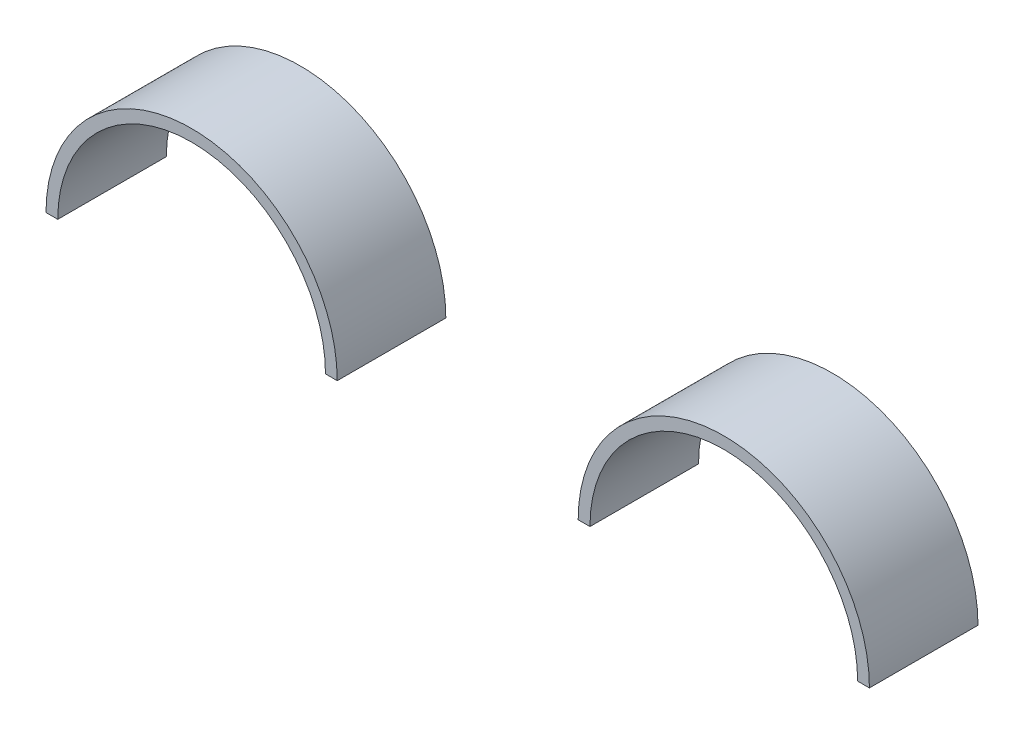
SolidWorks part; units mm, degrees
material "Velcro"
ref_plane "Front Plane" through (0, 0, 0) normal (0, 0, 1) x (1, 0, 0)
ref_plane "Top Plane" through (0, 0, 0) normal (0, 1, 0) x (1, 0, 0)
ref_plane "Right Plane" through (0, 0, 0) normal (1, 0, 0) x (0, 0, -1)
sketch "Sketch1" plane through (0, 0, 563.2423) normal (0, 0, -1) x (0, -1, 0)
  line L0 (326.7906, -1399.2805) -> (326.7906, -1499.2805) construction
  line L1 (326.7906, -1399.2805) -> (326.7906, -1499.2805) construction
  line L2 (326.7906, -1598.0805) -> (326.7906, -1698.0805) construction
  line L3 (326.7906, -1598.0805) -> (326.7906, -1698.0805) construction
  line L4 (326.7906, -1394.8805) -> (326.7906, -1399.2805)
  line L5 (326.7906, -1503.6805) -> (326.7906, -1499.2805)
  line L6 (326.7906, -1698.0805) -> (326.7906, -1702.4805)
  line L7 (326.7906, -1593.6805) -> (326.7906, -1598.0805)
  arc A0 (326.7906, -1698.0805) -> (326.7906, -1598.0805) centre (326.7906, -1648.0805) cw
  arc A1 (326.7906, -1499.2805) -> (326.7906, -1399.2805) centre (326.7906, -1449.2805) cw
  arc A2 (326.7906, -1503.6805) -> (326.7906, -1394.8805) centre (326.7906, -1449.2805) cw
  arc A3 (326.7906, -1702.4805) -> (326.7906, -1593.6805) centre (326.7906, -1648.0805) cw
  dimension "D1" = 4.4
  dimension "D2" = 4.4
extrude "Boss-Extrude1" add sketch "Sketch1" along normal blind 40.56
